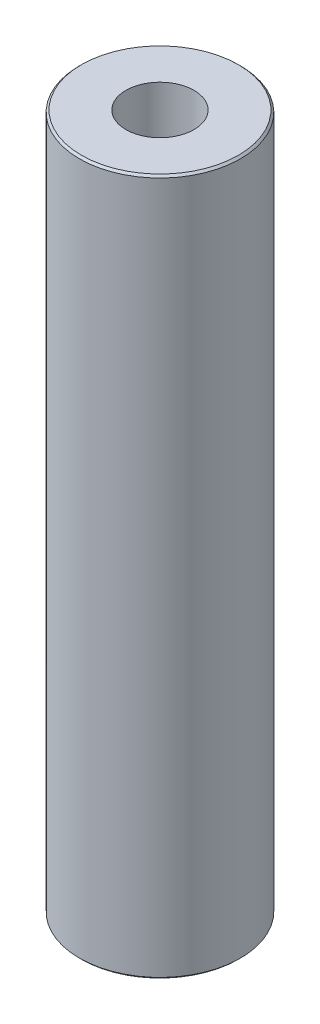
SolidWorks part; units mm, degrees
ref_plane "Front Plane" through (0, 0, 0) normal (0, 0, 1) x (1, 0, 0)
ref_plane "Top Plane" through (0, 0, 0) normal (0, 1, 0) x (1, 0, 0)
ref_plane "Right Plane" through (0, 0, 0) normal (1, 0, 0) x (0, 0, -1)
sketch "Sketch1" plane through (0, 0, 0) normal (0, 1, 0) x (1, 0, 0)
  circle A0 centre (0, 0) radius 52.5
  dimension "SHAFT_OD" = 105
extrude "Boss-Extrude1" add sketch "Sketch1" along normal blind 454.01
sketch "Sketch2" plane through (0, 0, 0) normal (0, 1, 0) x (1, 0, 0)
  circle A0 centre (0, 0) radius 22.2015
  dimension "BORE_D" = 44.4029
extrude "Cut-Extrude1" cut sketch "Sketch2" along normal through all
chamfer "Chamfer1" distance 1.3226 angle 45 2 edges at (0, 454.01, 52.5) (0, 0, 52.5)
